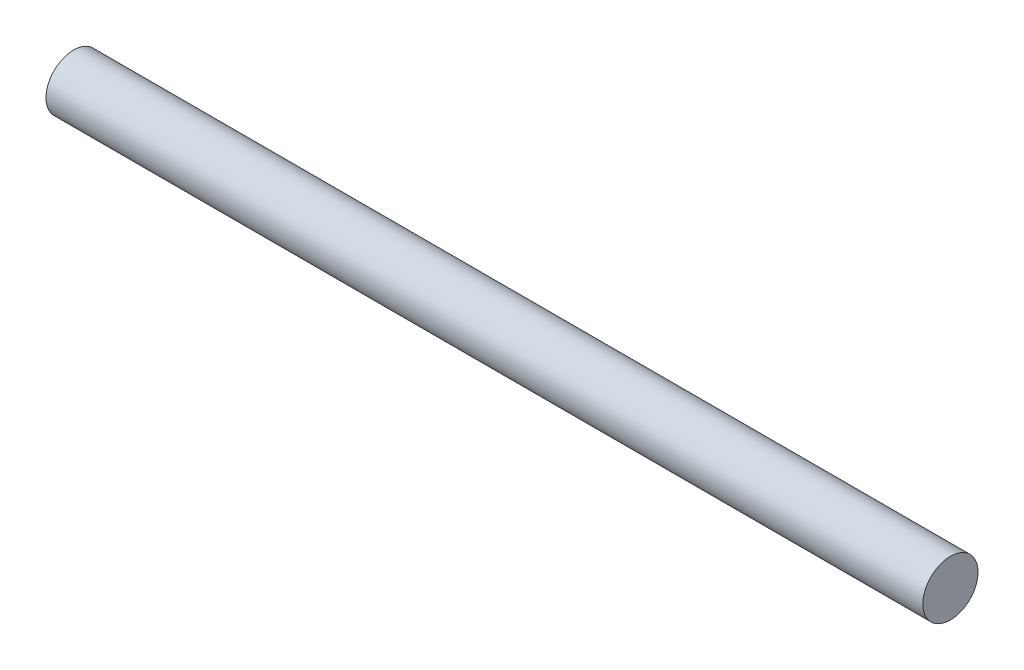
SolidWorks part; units mm, degrees
ref_plane "前视基准面" through (0, 0, 0) normal (0, 0, 1) x (1, 0, 0)
ref_plane "上视基准面" through (0, 0, 0) normal (0, 1, 0) x (1, 0, 0)
ref_plane "右视基准面" through (0, 0, 0) normal (1, 0, 0) x (0, 0, -1)
sketch "草图1" plane through (0, 0, 0) normal (1, 0, 0) x (0, 0, -1)
  circle A0 centre (0, 0) radius 4
  dimension "D1" = 8
extrude "凸台-拉伸1" add sketch "草图1" along normal up to surface (127 mm away)
